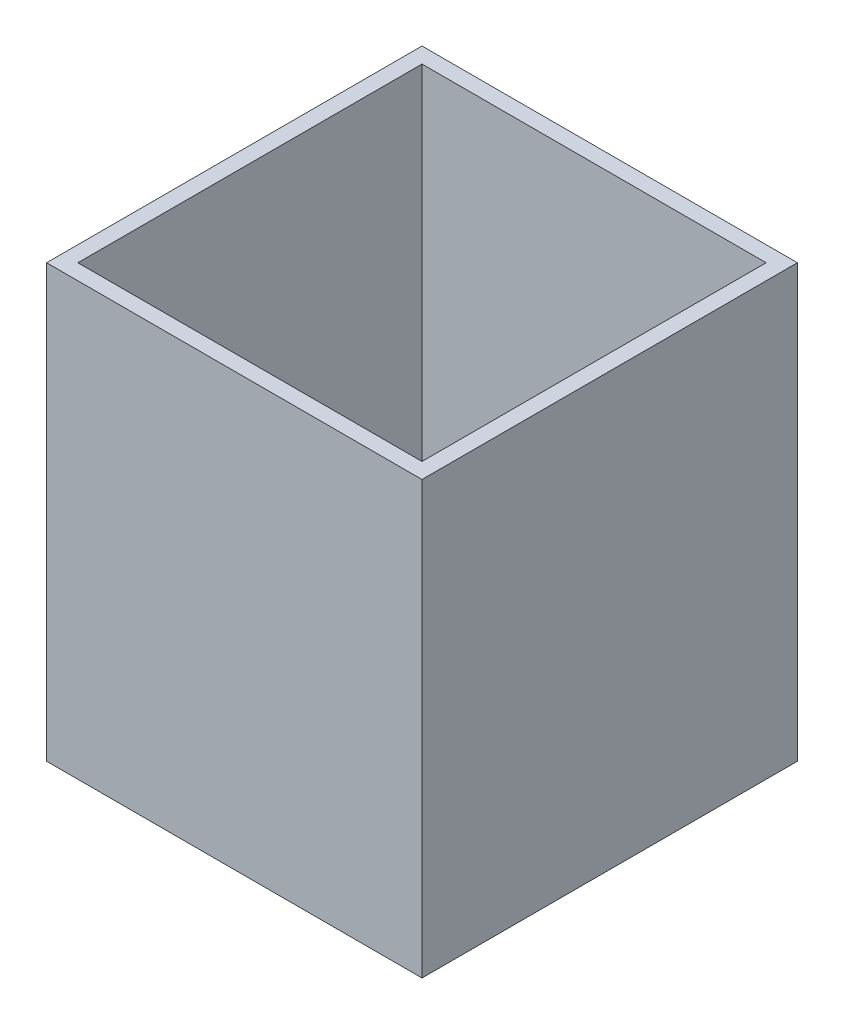
SolidWorks part; units mm, degrees
material "ABS"
ref_plane "Front Plane" through (0, 0, 0) normal (0, 0, 1) x (1, 0, 0)
ref_plane "Top Plane" through (0, 0, 0) normal (0, 1, 0) x (1, 0, 0)
ref_plane "Right Plane" through (0, 0, 0) normal (1, 0, 0) x (0, 0, -1)
sketch "Sketch1" plane through (0, 0, 0) normal (0, 1, 0) x (1, 0, 0)
  line L1 (30, -30) -> (-30, -30)
  line L2 (30, -30) -> (30, 30)
  line L3 (30, 30) -> (-30, 30)
  line L4 (-30, -30) -> (-30, 30)
  line L5 (30, -30) -> (-30, 30) construction
  line L6 (30, 30) -> (-30, -30) construction
  point P0 (0, 0)
  dimension "D1" = 60
  dimension "D2" = 60
extrude "Boss-Extrude1" add sketch "Sketch1" along normal blind 69
sketch "Sketch2" plane through (0, 69, 0) normal (0, 1, 0) x (1, 0, 0)
  line L1 (27.5, -27.5) -> (-27.5, -27.5)
  line L2 (27.5, -27.5) -> (27.5, 27.5)
  line L3 (27.5, 27.5) -> (-27.5, 27.5)
  line L4 (-27.5, -27.5) -> (-27.5, 27.5)
  line L5 (27.5, -27.5) -> (-27.5, 27.5) construction
  line L6 (27.5, 27.5) -> (-27.5, -27.5) construction
  point P0 (0, 0)
  dimension "D1" = 55
  dimension "D2" = 55
extrude "Cut-Extrude1" cut sketch "Sketch2" against normal blind 66.5
sketch "shaft axis" plane through (0, 0, 0) normal (0, 0, 1) x (1, 0, 0)
  line L1 (0, 2.5) -> (0, 81.7337)
  line L2 (27.5, 2.5) -> (-27.5, 2.5) construction
sketch "motor axis" plane through (0, 0, 0) normal (0, 0, 1) x (1, 0, 0)
  line L0 (3.5, 2.5) -> (3.5, 81.7337)
  line L1 (27.5, 2.5) -> (-27.5, 2.5) construction
  line L2 (0, 2.5) -> (0, 81.7337) construction
  dimension "D1" = 3.5
sketch "Sketch3" plane through (0, 2.5, 0) normal (0, 1, 0) x (1, 0, 0)
  line L0 (-27.5, -27.5) -> (27.5, -27.5) construction
  circle A0 centre (16.36, 2.5) radius 1.5
  circle A1 centre (16.36, -2.5) radius 1.5
  point P0 (16.36, 2.5)
  point P2 (16.36, -2.5)
  dimension "D1" = 25
  dimension "D2" = 5
  dimension "D3" = 3
  dimension "D4" = 16.36
extrude "Cut-Extrude2" cut sketch "Sketch3" against normal blind 1.875
thread "Thread4" pitch 0.5 method cut profile "Thread Profile5" start angle 0, offset 0, length 0, pitch 0.5, diameter 3
ref_plane "Plane5" through (14.86, 2.5, -2.5) normal (0, 0, 1) x (-1, 0, 0)
sketch "Thread Profile5" plane through (14.86, 2.5, -2.5) normal (0, 0, 1) x (-1, 0, 0)
  line L0 (0, 0) -> (0, 0.5) construction
  line L1 (0, 0) -> (0.2706, 0.1562)
  line L2 (0.2706, 0.1562) -> (0.2706, 0.2187)
  line L3 (0.2706, 0.2187) -> (0, 0.375)
  line L4 (0.2706, 0.1875) -> (0, 0.1875) construction
  line L11 (0, 0) -> (0, 0.375)
  point P2 (0, 0)
  dimension "Pitch" = 0.5
  dimension "Profile_Angle" = 60
  dimension "Profile_Land" = 0.0625
  dimension "Profile_Height" = 0.2706
thread "Thread5" pitch 0.5 method cut profile "Thread Profile6" start angle 0, offset 0, length 0, pitch 0.5, diameter 3
ref_plane "Plane6" through (14.86, 2.5, 2.5) normal (0, 0, 1) x (-1, 0, 0)
sketch "Thread Profile6" plane through (14.86, 2.5, 2.5) normal (0, 0, 1) x (-1, 0, 0)
  line L0 (0, 0) -> (0, 0.5) construction
  line L1 (0, 0) -> (0.2706, 0.1562)
  line L2 (0.2706, 0.1562) -> (0.2706, 0.2187)
  line L3 (0.2706, 0.2187) -> (0, 0.375)
  line L4 (0.2706, 0.1875) -> (0, 0.1875) construction
  line L11 (0, 0) -> (0, 0.375)
  point P2 (0, 0)
  dimension "Pitch" = 0.5
  dimension "Profile_Angle" = 60
  dimension "Profile_Land" = 0.0625
  dimension "Profile_Height" = 0.2706
